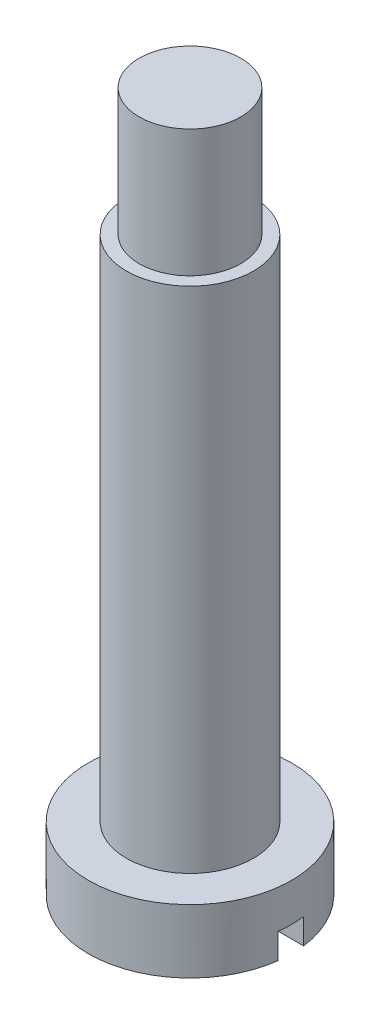
SolidWorks part; units mm, degrees
ref_plane "前视基准面" through (0, 0, 0) normal (0, 0, 1) x (1, 0, 0)
ref_plane "上视基准面" through (0, 0, 0) normal (0, 1, 0) x (1, 0, 0)
ref_plane "右视基准面" through (0, 0, 0) normal (1, 0, 0) x (0, 0, -1)
other "Configuration Table"
sketch "草图1" plane through (0, 0, 0) normal (0, 1, 0) x (1, 0, 0)
  circle A0 centre (0, 0) radius 4
  dimension "D1" = 8
extrude "凸台-拉伸1" add sketch "草图1" against normal blind 2.5
sketch "草图2" plane through (0, 0, 0) normal (0, 1, 0) x (1, 0, 0)
  circle A0 centre (0, 0) radius 2.5
  dimension "D1" = 5
extrude "凸台-拉伸2" add sketch "草图2" along normal blind 20 contours A0
sketch "草图3" plane through (0, 20, 0) normal (0, 1, 0) x (1, 0, 0)
  circle A0 centre (0, 0) radius 2
  dimension "D1" = 4
extrude "凸台-拉伸3" add sketch "草图3" along normal blind 5
sketch "草图4" plane through (0, -2.5, 0) normal (0, -1, 0) x (1, 0, 0)
  line L0 (-4, 0) -> (4, 0)
  circle A0 centre (0, 0) radius 4 construction
extrude "切除-拉伸-薄壁1" cut sketch "草图4" against normal blind 1 and the other way through all thin thin type mid plane wall 1
ref_axis "基准轴1" through (0, 29.9074, 0) along (0, -1, 0)
